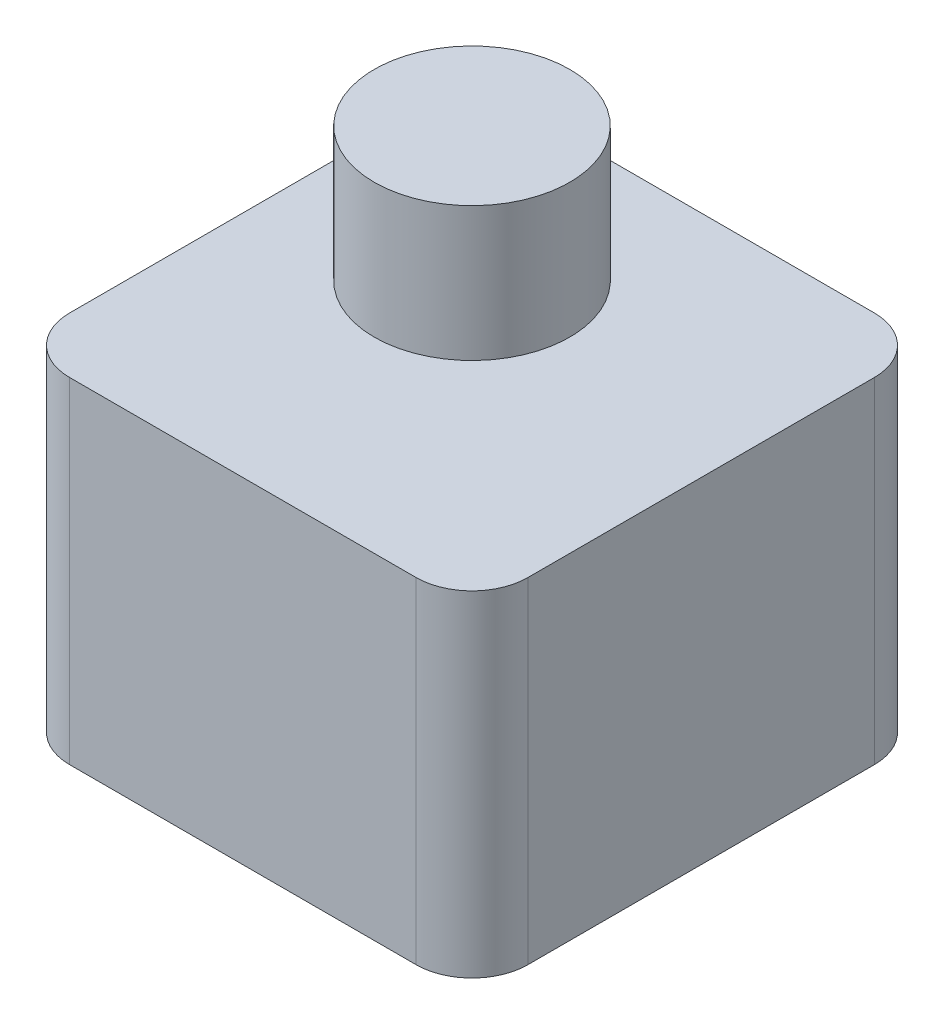
SolidWorks part; units mm, degrees
ref_plane "Alzado" through (0, 0, 0) normal (0, 0, 1) x (1, 0, 0)
ref_plane "Planta" through (0, 0, 0) normal (0, 1, 0) x (1, 0, 0)
ref_plane "Vista lateral" through (0, 0, 0) normal (1, 0, 0) x (0, 0, -1)
sketch "Croquis2" plane through (0, 0, 0) normal (0, 1, 0) x (1, 0, 0)
  line L1 (5, 41) -> (36, 41)
  line L2 (0, 36) -> (0, 5)
  line L3 (5, 0) -> (36, 0)
  line L4 (41, 36) -> (41, 5)
  arc A0 (0, 5) -> (5, 0) centre (5, 5) ccw
  arc A1 (36, 0) -> (41, 5) centre (36, 5) ccw
  arc A2 (36, 41) -> (41, 36) centre (36, 36) cw
  arc A3 (5, 41) -> (0, 36) centre (5, 36) ccw
  point P4 (0, 0)
  point P5 (1.8114, 0)
  point P6 (0, 0)
  point P7 (0, 0)
  point P8 (-34.4166, -21.5103)
  point P9 (-61.5875, -1.585)
  point P10 (-72.4559, 3.8492)
  point P12 (0, 27.6238)
  point P13 (0, 0)
  point P14 (0, 0)
  point P15 (0, 0)
  point P16 (0, 0)
  dimension "D1" = 5
  dimension "D2" = 41
  dimension "D3" = 41
extrude "Saliente-Extruir2" add sketch "Croquis2" along normal blind 30
sketch "Croquis3" plane through (0, 30, 0) normal (0, 1, 0) x (1, 0, 0)
  circle A3 centre (20.5, 20.5) radius 1.5
extrude "Saliente-Extruir3" add sketch "Croquis3" along normal blind 17 separate body
ref_plane "Plano2" through (0, 35, 0) normal (0, 1, 0) x (1, 0, 0)
sketch "Croquis6" plane through (0, 35, 0) normal (0, 1, 0) x (1, 0, 0)
  circle A0 centre (20.5, 20.5) radius 8.75
extrude "Saliente-Extruir4" add sketch "Croquis6" along normal blind 12
